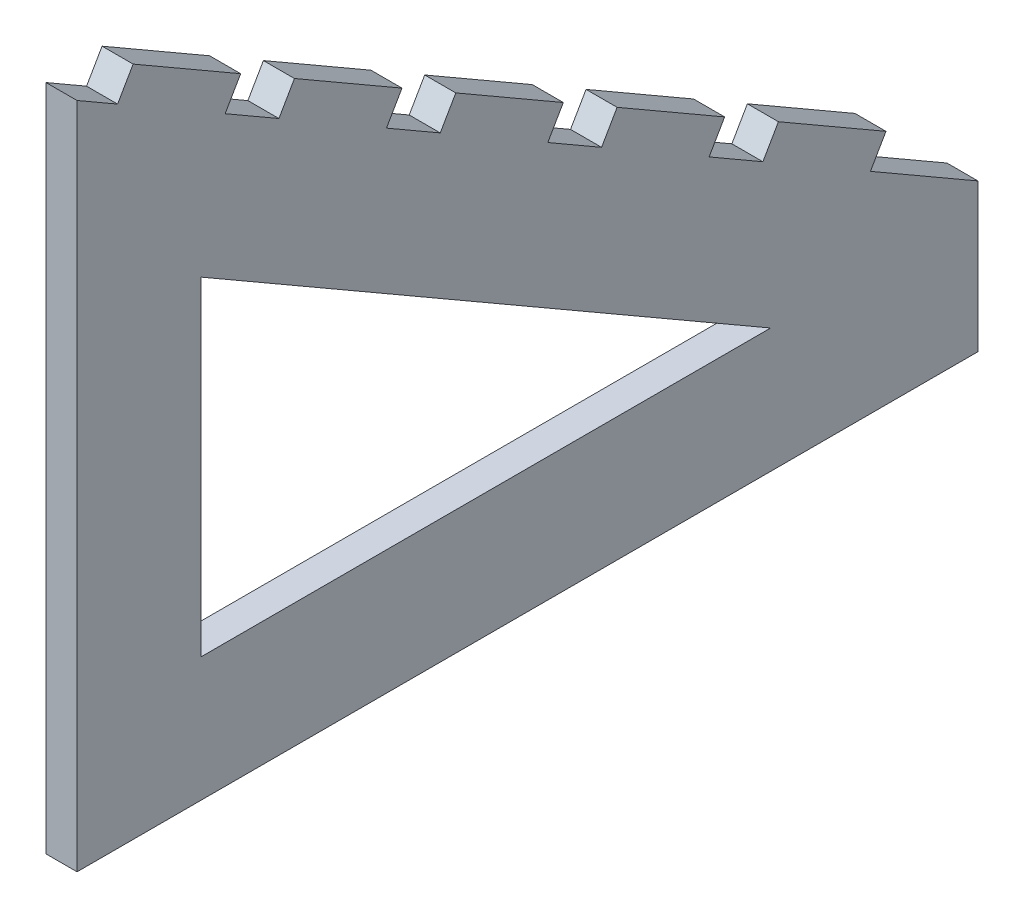
SolidWorks part; units mm, degrees
ref_plane "Front Plane" through (0, 0, 0) normal (0, 0, 1) x (1, 0, 0)
ref_plane "Top Plane" through (0, 0, 0) normal (0, 1, 0) x (1, 0, 0)
ref_plane "Right Plane" through (0, 0, 0) normal (1, 0, 0) x (0, 0, -1)
sketch "Sketch1" plane through (-32.0384, 0, 0) normal (-1, 0, 0) x (0, 0, 1)
  line L0 (-213.5096, 95.25) -> (-213.5096, 125.4926)
  line L1 (165.3114, 95.25) -> (-69.85, 95.25) construction
  line L2 (-213.5096, 125.4926) -> (-29.2385, 231.8816)
  line L3 (-29.2385, 231.8816) -> (-29.2385, 95.25)
  line L4 (-29.2385, 95.25) -> (-213.5096, 95.25)
  line L5 (-29.2385, 231.8816) -> (-53.8489, 217.6728) construction
  line L6 (-29.2385, 95.25) -> (-29.2385, 231.8816) construction
extrude "Boss-Extrude1" add sketch "Sketch1" along normal mid plane 6.35
sketch "Sketch2" plane through (-35.2134, 0, 0) normal (-1, 0, 0) x (0, 0, 1)
  line L14 (-54.6385, 120.65) -> (-54.6385, 187.8875)
  line L15 (-171.0972, 120.65) -> (-54.6385, 120.65)
  line L16 (-54.6385, 187.8875) -> (-171.0972, 120.65)
  line L17 (-54.6385, 120.65) -> (-54.6385, 187.8875)
  line L18 (-171.0972, 120.65) -> (-54.6385, 120.65)
  line L19 (-54.6385, 187.8875) -> (-171.0972, 120.65)
  dimension "D1" = 25.4
extrude "Cut-Extrude1" cut sketch "Sketch2" against normal blind 6.35
sketch "Sketch3" plane through (0, 186.5718, -107.7173) normal (0, 0.866, -0.5) x (1, 0, 0)
  line L0 (-35.2134, -90.6195) -> (-35.2134, 122.1584) construction
  line L1 (-35.2134, 96.7584) -> (-28.8634, 96.7584)
  line L2 (-35.2134, 96.7584) -> (-35.2134, 71.3584)
  line L3 (-35.2134, 71.3584) -> (-28.8634, 71.3584)
  line L4 (-28.8634, 96.7584) -> (-28.8634, 71.3584)
  line L5 (-28.8634, -90.6195) -> (-28.8634, 122.1584) construction
  dimension "D1" = 25.4
  dimension "D2" = 25.4
extrude "Boss-Extrude2" add sketch "Sketch3" along normal blind 6.35
pattern_linear "LPattern1" count 5 spacing 38.1 along (0, 0.5, 0.866) of "Boss-Extrude2"
